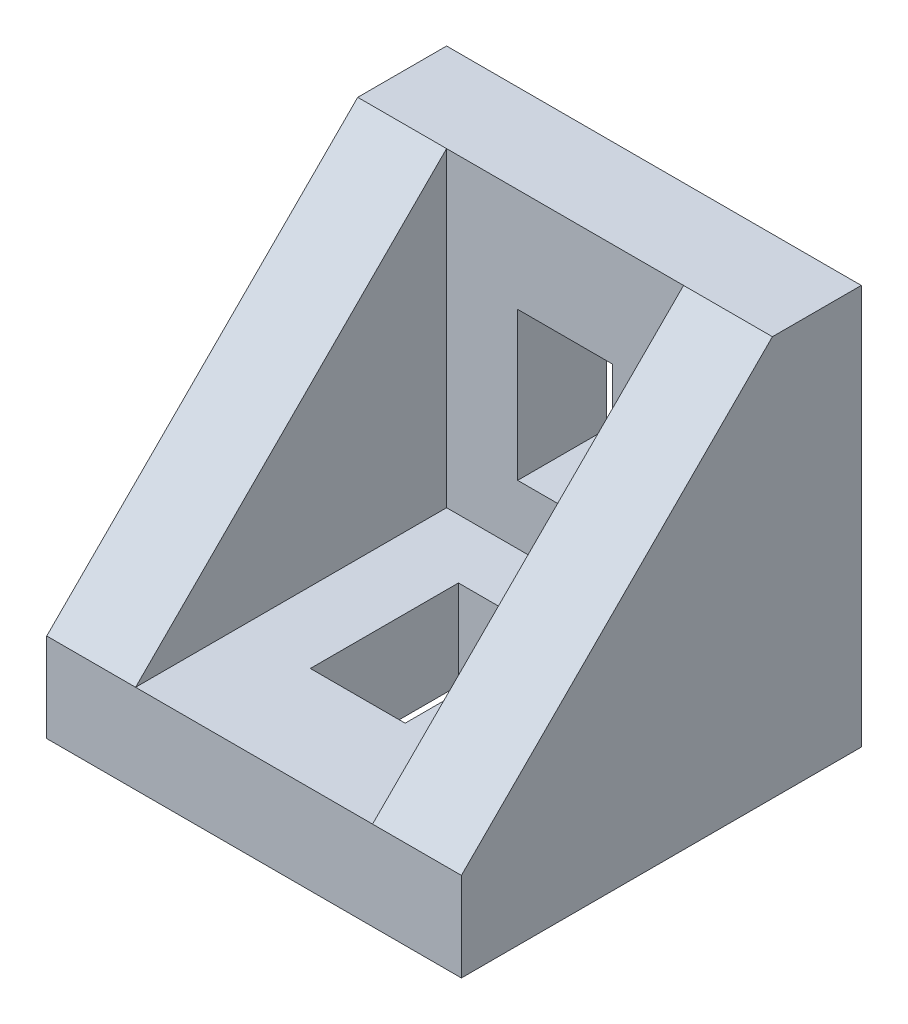
SolidWorks part; units mm, degrees
ref_plane "Alzado" through (0, 0, 0) normal (0, 0, 1) x (1, 0, 0)
ref_plane "Planta" through (0, 0, 0) normal (0, 1, 0) x (1, 0, 0)
ref_plane "Vista lateral" through (0, 0, 0) normal (1, 0, 0) x (0, 0, -1)
sketch "Croquis1" plane through (0, 0, 0) normal (1, 0, 0) x (0, 0, -1)
  line L0 (0, 0) -> (27, 0)
  line L1 (27, 0) -> (27, 27)
  line L7 (0, 6) -> (0, 0)
  line L9 (27, 27) -> (21, 27)
  line L10 (21, 27) -> (0, 6)
  dimension "D1" = 27
  dimension "D2" = 27
  dimension "D3" = 6
  dimension "D4" = 6
extrude "Saliente-Extruir1" add sketch "Croquis1" along normal blind 28 contours L0 L1 region at (0, 10.6814, -16.3186)
shell "Vaciado2" thickness 6 removed face at (14, 16.5, -10.5) removed face at (14, 27, -24) removed face at (14, 3, 0)
sketch "Croquis2" plane through (0, 0, -21) normal (0, 0, 1) x (1, 0, 0)
  line L0 (28, 0) -> (0, 0) construction
  line L1 (10.8, 20) -> (17.2, 20)
  line L2 (10.8, 20) -> (10.8, 10)
  line L3 (10.8, 10) -> (17.2, 10)
  line L4 (17.2, 20) -> (17.2, 10)
  point P6 (14, 0)
  point P7 (14, 10)
  dimension "D1" = 10
  dimension "D2" = 6.4
  dimension "D3" = 20
extrude "Cortar-Extruir1" cut sketch "Croquis2" against normal up to next
sketch "Croquis4" plane through (0, 6, 0) normal (0, 1, 0) x (1, 0, 0)
  line L0 (10.8, 17) -> (17.2, 17)
  line L1 (10.8, 17) -> (10.8, 7)
  line L2 (10.8, 7) -> (17.2, 7)
  line L3 (17.2, 17) -> (17.2, 7)
  line L4 (28, 27) -> (0, 27) construction
  point P7 (14, 27)
  point P8 (14, 17)
  dimension "D1" = 10
  dimension "D2" = 6.4
  dimension "D3" = 20
extrude "Cortar-Extruir2" cut sketch "Croquis4" against normal up to next
